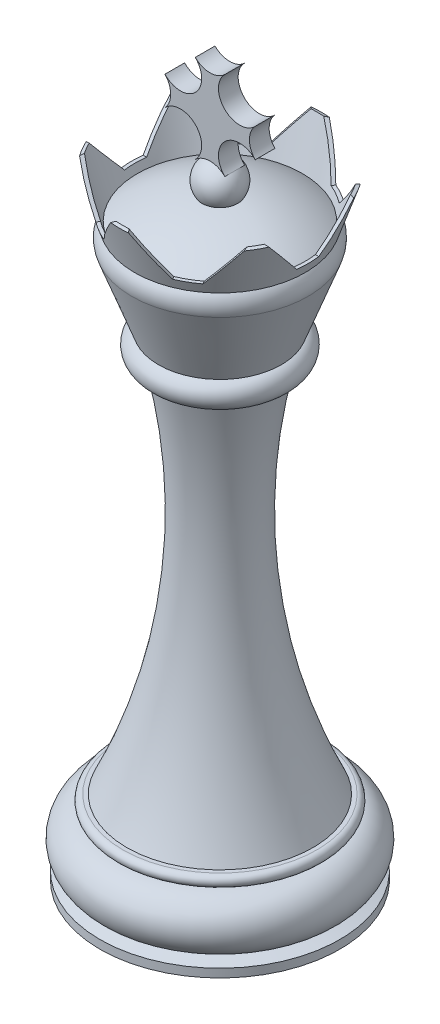
SolidWorks part; units mm, degrees
ref_plane "Front Plane" through (0, 0, 0) normal (0, 0, 1) x (1, 0, 0)
ref_plane "Top Plane" through (0, 0, 0) normal (0, 1, 0) x (1, 0, 0)
ref_plane "Right Plane" through (0, 0, 0) normal (1, 0, 0) x (0, 0, -1)
sketch "Sketch1" plane through (0, 0, 0) normal (0, 0, 1) x (1, 0, 0)
  line L0 (0, 0) -> (0, -19.2438) construction
  line L1 (0, 0) -> (12.5016, 0)
  line L2 (12.4781, -1.4284) -> (12.4781, -1.4919)
  line L3 (0, -9.6219) -> (15.4504, -9.6219)
  line L4 (15.4504, -9.6219) -> (15.4504, -8.5301)
  line L5 (15.4504, -8.5301) -> (13.8939, -8.0177)
  line L6 (0, 0) -> (0, -9.6219)
  line L7 (0, -9.6219) -> (0, 67.1777) construction
  line L8 (12.5819, 69.7609) -> (10.6346, 63.9072)
  line L9 (11.9998, 62.887) -> (7.9115, 51.8351)
  line L10 (12.9783, 69.629) -> (10.9921, 63.6583)
  line L12 (0, 0) -> (0, -9.6219)
  line L13 (0, 67.1777) -> (0, 0)
  line L14 (11.9998, 62.887) -> (0, 62.887)
  line L18 (0, 67.1777) -> (0, 83.8233) construction
  line L19 (-24.4756, 76.1676) -> (25.7476, 76.1676) construction
  line L20 (0, 71.2468) -> (0, 64.3767)
  line L21 (12.5819, 69.7609) -> (12.9783, 69.629)
  arc A0 (12.5016, 0) -> (12.4781, -1.4284) centre (12.5016, -0.7144) cw
  arc A1 (13.8939, -8.0177) -> (12.4781, -1.4919) centre (12.4226, -4.9204) ccw
  arc A3 (7.9115, 51.8351) -> (6.9011, 48.4918) centre (7.3045, 50.1942) cw
  arc A4 (0, 67.1777) -> (11.9998, 62.887) centre (0, 48.2522) cw
  arc A8 (1.9087, 70.4706) -> (-1.9087, 70.4706) centre (0, 68.5118) ccw
  arc A10 (6.9011, 48.4918) -> (11.9974, 0) centre (79.7902, 31.6385) ccw
  arc A21 (5.8139, 78.0367) -> (5.8139, 74.2985) centre (7.8104, 76.1676) ccw
  arc A23 (-1.9087, 81.8646) -> (1.9087, 81.8646) centre (0, 83.8233) ccw
  arc A24 (-5.8139, 74.2985) -> (-5.8139, 78.0367) centre (-7.8104, 76.1676) ccw
  arc A25 (-5.8139, 78.0367) -> (-1.9087, 81.8646) centre (-3.8173, 79.9058) ccw
  arc A26 (1.9087, 81.8646) -> (5.8139, 78.0367) centre (3.8173, 79.9058) ccw
  arc A27 (-1.9087, 70.4706) -> (-5.8139, 74.2985) centre (-3.8173, 72.4294) ccw
  arc A28 (5.8139, 74.2985) -> (1.9087, 70.4706) centre (3.8173, 72.4294) ccw
  arc A29 (1.9087, 70.4706) -> (-1.9087, 70.4706) centre (0, 68.5118) ccw
  circle A30 centre (0, 68.5118) radius 2.7349
  point P23 (12.6756, 62.6075)
  point P28 (0, 84.1311)
  point P33 (11.2057, 63.7204)
  point P36 (11.7727, 63.3215)
  point P41 (11.9974, 62.8805)
  point P46 (7.8104, 76.1676)
  point P50 (13.7944, 69.3575)
  point P52 (11.0229, 63.6074)
  point P54 (11.4084, 63.3135)
  point P55 (10.621, 63.8661)
  point P56 (10.9921, 63.6583)
  dimension "D1" = 0.0635
  dimension "D4" = 0.7144
  dimension "D3" = 3.429
  dimension "D6" = 2.7349
  dimension "D2" = 12.5016
  dimension "D5" = 9.6219
revolve "Revolve1" add sketch "Sketch1" angle 360 about L0 region at (4.0013, 31.717, 0) region at (7.4657, -4.9178, 0) region at (11.7975, 66.7389, 0)
sketch "Sketch8" plane through (0, 0, 0) normal (1, 0, 0) x (0, 0, -1)
  line L0 (-1.4288, 64.8973) -> (1.4288, 64.8973)
  line L1 (0, 72.9777) -> (0, -12.7055) construction
  line L2 (-1.4288, 64.8973) -> (-5.9725, 70.2398)
  line L3 (-5.9725, 70.2398) -> (5.9725, 70.2398)
  line L4 (5.9725, 70.2398) -> (1.4288, 64.8973)
  point P2 (1.0238, 64.9489)
  point P4 (5.9725, 70.2398)
  point P8 (1.4288, 64.8973)
extrude "Cut-Extrude2" cut sketch "Sketch8" along normal through all
pattern_circular "CirPattern1" count 6 over 360 about axis through (0, -9.6219, 0) along (0, 1, 0) of "Cut-Extrude2"
revolve "Revolve2" add sketch "Sketch1<10>" angle 360 about L18 region at (4.8297, 64.4868, 0) region at (1.2241, 68.9734, 0)
sketch "Sketch1<10>" plane through (0, 0, 0) normal (0, 0, 1) x (1, 0, 0) same geometry as "Sketch1"
extrude "Boss-Extrude2" add sketch "Sketch1<11>" along normal mid plane 2.54 separate body contours A27 A24 A25 A23 A26 A21 A28 A29
sketch "Sketch1<11>" plane through (0, 0, 0) normal (0, 0, 1) x (1, 0, 0) same geometry as "Sketch1"
fillet "Fillet2" radius 2.54 1 edges at (0, 62.887, 11.9998)
